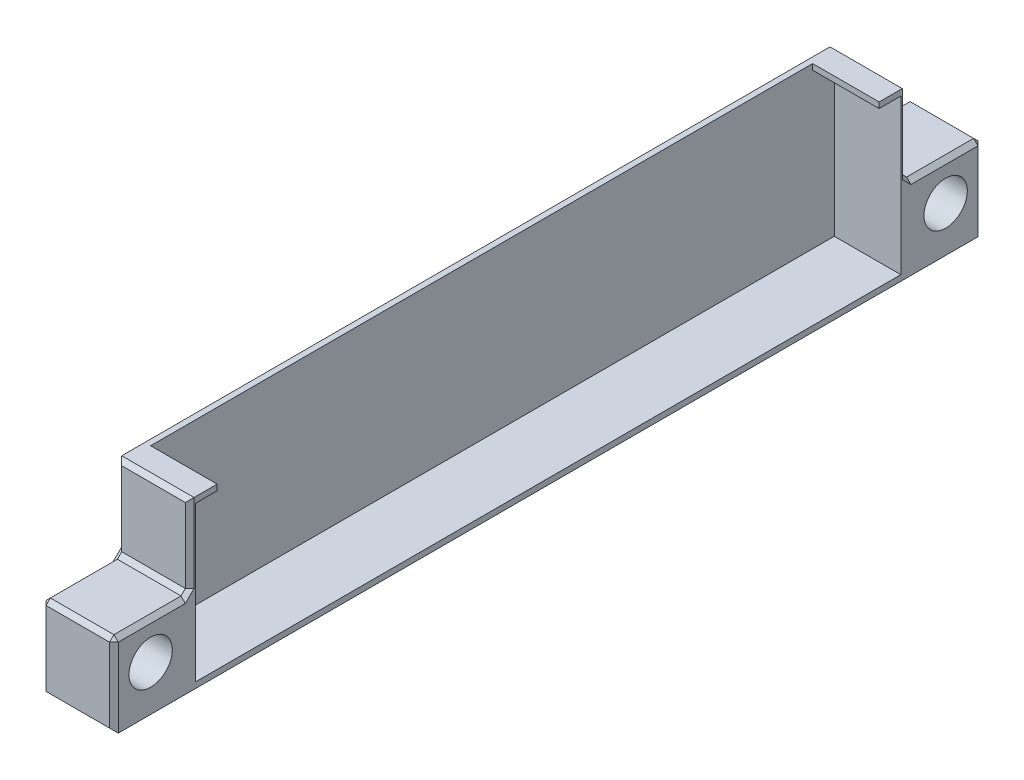
SolidWorks part; units mm, degrees
ref_plane "Alzado" through (0, 0, 0) normal (0, 0, 1) x (1, 0, 0)
ref_plane "Planta" through (0, 0, 0) normal (0, 1, 0) x (1, 0, 0)
ref_plane "Vista lateral" through (0, 0, 0) normal (1, 0, 0) x (0, 0, -1)
sketch "Croquis1" plane through (0, 0, 0) normal (0, 0, 1) x (1, 0, 0)
  line L0 (0, 0) -> (0, 115)
  line L1 (0, 0) -> (50, 0)
  line L2 (4, 4) -> (50, 4)
  line L3 (4, 4) -> (4, 115)
  line L4 (0, 115) -> (4, 115)
  line L5 (50, 4) -> (50, 0)
  dimension "D1" = 115
  dimension "D2" = 50
  dimension "D3" = 4
extrude "Saliente-Extruir1" add sketch "Croquis1" along normal blind 248 and the other way blind 248
sketch "Croquis2" plane through (0, 0, 248) normal (0, 0, 1) x (1, 0, 0)
  line L0 (0, 57.5) -> (25, 57.5) construction
  line L1 (0, 115) -> (0, 0) construction
  line L2 (25, 57.5) -> (25, 0) construction
  line L3 (0, 0) -> (50, 0) construction
  line L5 (0, 115) -> (50, 115)
  line L6 (0, 115) -> (0, 0)
  line L7 (0, 0) -> (50, 0)
  line L8 (50, 115) -> (50, 0)
  line L9 (0, 115) -> (50, 0) construction
  line L10 (0, 0) -> (50, 115) construction
extrude "Saliente-Extruir2" add sketch "Croquis2" against normal blind 4
sketch "Croquis3" plane through (50, 0, 0) normal (1, 0, 0) x (0, 0, -1)
  line L0 (248, 0) -> (-248, 0) construction
  line L1 (-248, 0) -> (-248, 115) construction
  line L2 (248, 0) -> (-248, 0)
  line L3 (-248, 0) -> (-248, 115)
  line L4 (-248, 0) -> (-300.4, 0)
  line L5 (-300.4, 0) -> (-300.4, 57.5)
  line L6 (-300.4, 57.5) -> (-248, 57.5)
  line L7 (-316.3335, 50) -> (-127.1391, 50) construction
  line L8 (-332.8582, 21.988) -> (-171.3057, 21.988) construction
  dimension "D1" = 52.4
extrude "Saliente-Extruir3" add sketch "Croquis3" against normal up to surface (50 mm away) contours L6 L5 L4 L3 region at (50, 28.75, 274.2) up to face at (0, 57.5, 0)
sketch "Croquis4" plane through (4, 0, 0) normal (1, 0, 0) x (0, 0, -1)
  line L0 (-244, 4) -> (-244, 115) construction
  line L1 (-244, 4) -> (-244, 115)
  line L2 (-300.4, 57.5) -> (-248, 57.5) construction
  line L3 (-244, 115) -> (-191.6, 115)
  line L4 (-244, 115) -> (-244, 57.5)
  line L5 (-244, 57.5) -> (-191.6, 57.5)
  line L6 (-191.6, 115) -> (-191.6, 57.5)
  line L7 (-300.4, 57.5) -> (-248, 57.5)
  dimension "D1" = 52.4
mirror "Simetría1" about plane through (0, 0, 0) normal (0, 0, 1) of "Saliente-Extruir2", "Saliente-Extruir3"
sketch "Croquis5" plane through (0, 115, 0) normal (0, 1, 0) x (1, 0, 0)
  line L0 (50, -244) -> (4, -244) construction
  line L1 (50, -244) -> (4, -244)
  line L3 (50, -244) -> (4, -244)
  line L4 (50, -244) -> (50, -229)
  line L5 (50, -229) -> (4, -229)
  line L6 (4, -244) -> (4, -229)
  line L7 (4, 244) -> (4, -244) construction
  line M12 (50, -244) -> (4, -244)
  dimension "D1" = 15
extrude "Saliente-Extruir5" add sketch "Croquis5" against normal blind 4 contours L4 L5 M12 region at (27, 115, 236.5)
mirror "Simetría2" about plane through (0, 0, 0) normal (0, 0, 1) of "Saliente-Extruir5"
chamfer "Chaflán1" distance 3 angle 45 21 edges at (50, 28.75, -300.4) (50, 86.25, -248) (25, 115, -248) (0, 86.25, -248) (50, 57.5, -274.2) (25, 57.5, -248) (0, 57.5, -274.2) (25, 57.5, -300.4) (0, 28.75, -300.4) (25, 0, -300.4) (25, 57.5, 248) (0, 86.25, 248) (25, 115, 248) (50, 86.25, 248) (0, 0, 0) (25, 0, 300.4) (50, 28.75, 300.4) (0, 28.75, 300.4) (50, 57.5, 274.2) (0, 57.5, 274.2) (25, 57.5, 300.4)
sketch "Croquis6" plane through (0, 0, 0) normal (-1, 0, 0) x (0, 0, 1)
  circle A1 centre (-275, 31.3) radius 5 construction
  circle A2 centre (-275, 31.3) radius 15
  circle A3 centre (-275, 31.3) radius 5 construction
  dimension "D1" = 30
extrude "Cortar-Extruir1" cut sketch "Croquis6" against normal up to surface (50 mm away) up to face at (50, 68.3, 0)
sketch "Croquis7" plane through (50, 0, 0) normal (1, 0, 0) x (0, 0, -1)
  circle A1 centre (-275, 31.3) radius 5 construction
  circle A2 centre (-275, 31.3) radius 15
  circle A3 centre (-275, 31.3) radius 5 construction
  dimension "D1" = 30
extrude "Cortar-Extruir2" cut sketch "Croquis7" against normal up to surface (50 mm away) up to face at (0, 31.3, -260)
